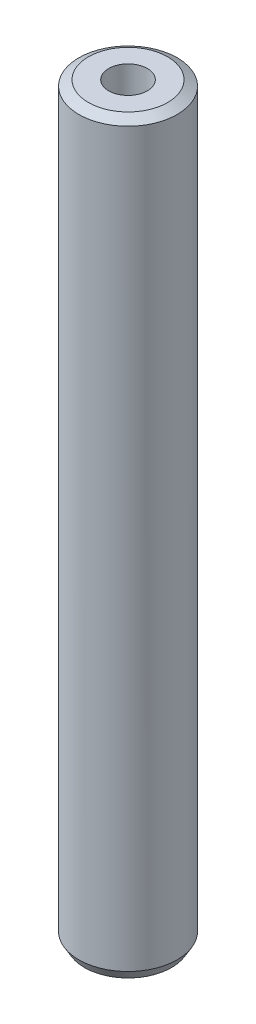
SolidWorks part; units mm, degrees
ref_plane "Front Plane" through (0, 0, 0) normal (0, 0, 1) x (1, 0, 0)
ref_plane "Top Plane" through (0, 0, 0) normal (0, 1, 0) x (1, 0, 0)
ref_plane "Right Plane" through (0, 0, 0) normal (1, 0, 0) x (0, 0, -1)
sketch "Sketch1" plane through (0, 0, 0) normal (0, 1, 0) x (1, 0, 0)
  circle A0 centre (0, 0) radius 27.5
  dimension "SHAFT_OD" = 55
extrude "Boss-Extrude1" add sketch "Sketch1" along normal blind 417.8477
sketch "Sketch2" plane through (0, 0, 0) normal (0, 1, 0) x (1, 0, 0)
  circle A0 centre (0, 0) radius 10.8239
  dimension "BORE_D" = 21.6479
extrude "Cut-Extrude1" cut sketch "Sketch2" along normal through all
chamfer "Chamfer1" distance 3.1218 angle 59.715 2 edges at (0, 417.8477, 27.5) (0, 0, 27.5) first distance on face at (0, 417.8477, 27.5) first distance on face at (0, 0, 10.8239)
